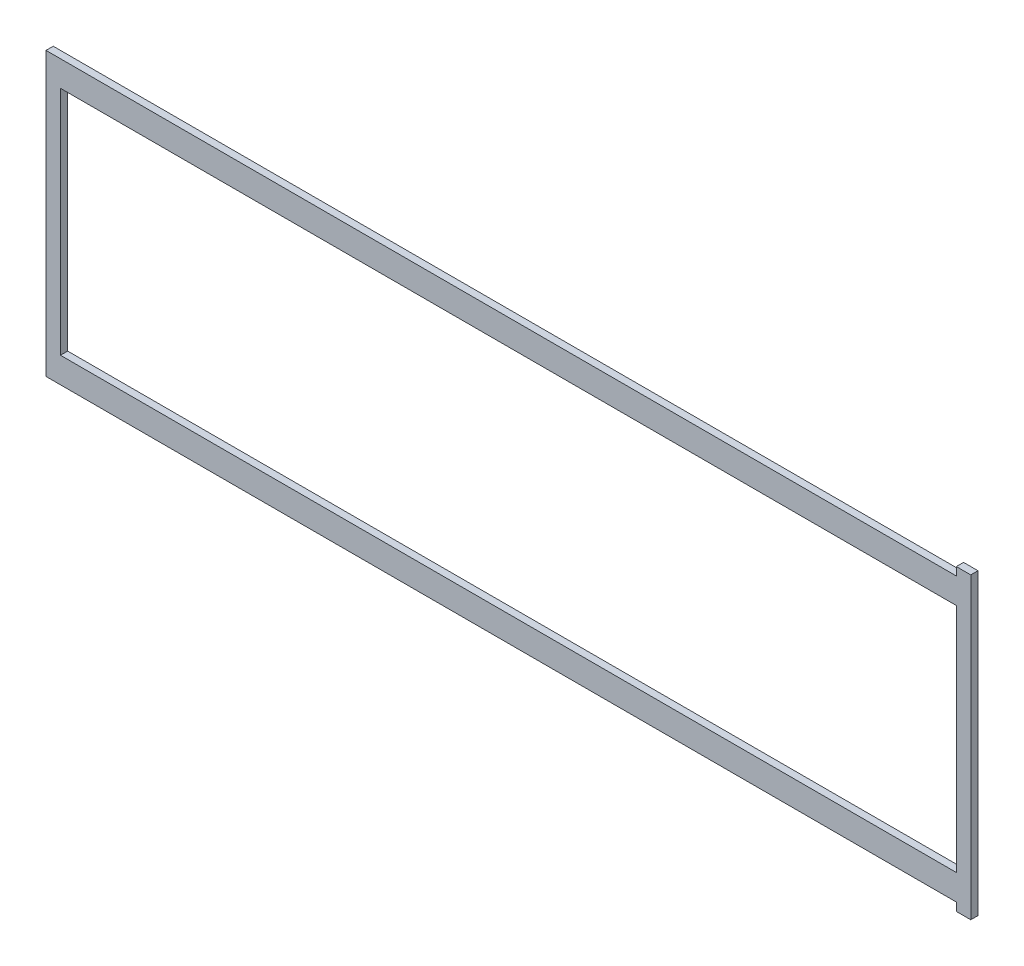
SolidWorks part; units mm, degrees
ref_plane "Front Plane" through (0, 0, 0) normal (0, 0, 1) x (1, 0, 0)
ref_plane "Top Plane" through (0, 0, 0) normal (0, 1, 0) x (1, 0, 0)
ref_plane "Right Plane" through (0, 0, 0) normal (1, 0, 0) x (0, 0, -1)
sketch "Sketch1" plane through (0, 0, 0) normal (0, 0, 1) x (1, 0, 0)
  line L0 (0, 62.0522) -> (406.4, 62.0522) construction
  line L1 (0, 0) -> (400.05, 0)
  line L2 (0, 0) -> (0, 124.1044)
  line L3 (0, 124.1044) -> (400.05, 124.1044)
  line L4 (406.4, 0) -> (406.4, 124.1044)
  line L6 (400.05, 124.1044) -> (400.05, 127.6858)
  line L7 (400.05, 127.6858) -> (406.4, 127.6858)
  line L8 (406.4, 124.1044) -> (406.4, 127.6858)
  line L9 (406.4, 0) -> (406.4, -3.5814)
  line L10 (400.05, -3.5814) -> (406.4, -3.5814)
  line L11 (400.05, 0) -> (400.05, -3.5814)
  line L13 (6.35, 112.8522) -> (400.05, 112.8522)
  line L14 (6.35, 112.8522) -> (6.35, 11.2522)
  line L15 (6.35, 11.2522) -> (400.05, 11.2522)
  line L16 (400.05, 112.8522) -> (400.05, 11.2522)
  point P17 (6.35, 62.0522)
  dimension "D1" = 406.4
  dimension "D2" = 124.1044
  dimension "D3" = 131.2672
  dimension "D4" = 6.35
  dimension "D5" = 6.35
  dimension "D6" = 6.35
  dimension "D7" = 101.6
extrude "Boss-Extrude1" add sketch "Sketch1" along normal blind 3.175 contours L0 L2 L1 L11 L10 L4 L16 L15 L14 | L2 L0 L14 L13 L16 L4 L7 L6 L3 region at (204.068, 114.6911, 0) region at (204.068, 9.4133, 0)
equation "\"ROADWIDTH\" = 4.886"
equation "\"TABWIDTH\" = 5.168"
equation "\"D2@Sketch1\"=\"ROADWIDTH\""
equation "\"D3@Sketch1\"=\"TABWIDTH\""
